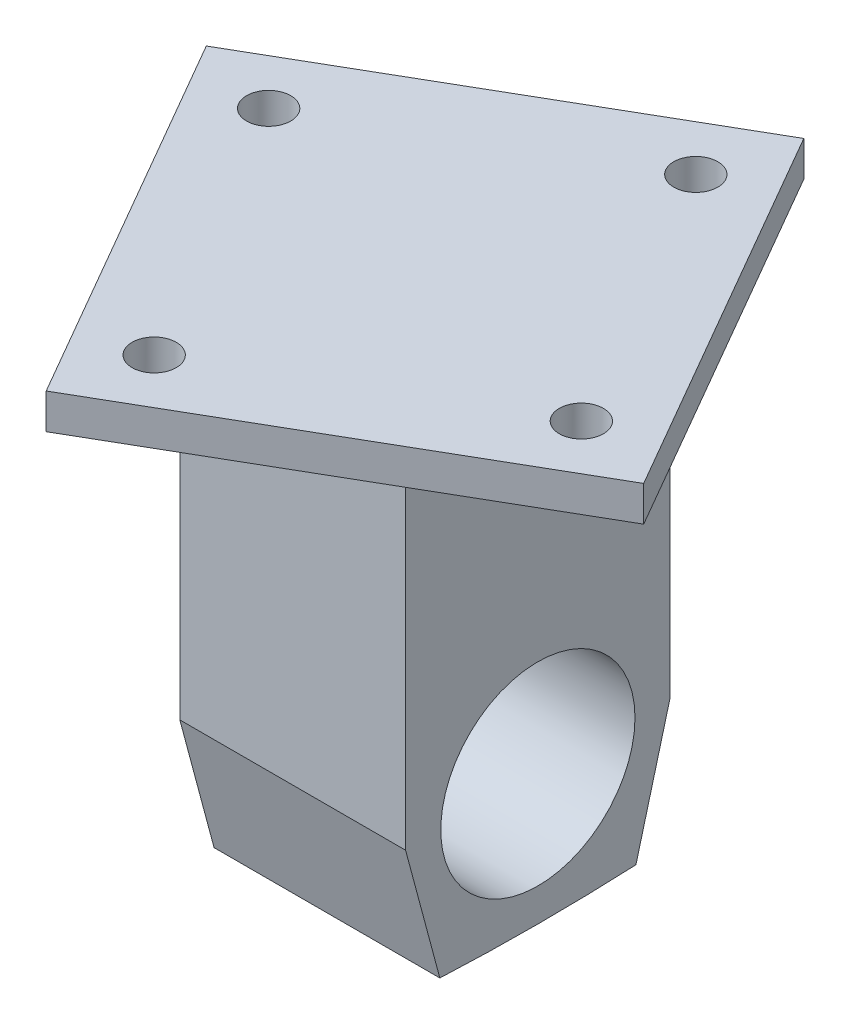
SolidWorks part; units mm, degrees
material "ABS"
ref_plane "Front Plane" through (0, 0, 0) normal (0, 0, 1) x (1, 0, 0)
ref_plane "Top Plane" through (0, 0, 0) normal (0, 1, 0) x (1, 0, 0)
ref_plane "Right Plane" through (0, 0, 0) normal (1, 0, 0) x (0, 0, -1)
sketch "Sketch1" plane through (0, 0, 0) normal (0, 1, 0) x (1, 0, 0)
  line L1 (-16.256, -19.05) -> (16.256, -19.05)
  line L2 (-16.256, -19.05) -> (-16.256, 19.05)
  line L3 (-16.256, 19.05) -> (16.256, 19.05)
  line L4 (16.256, -19.05) -> (16.256, 19.05)
  line L5 (-16.256, -19.05) -> (16.256, 19.05) construction
  line L6 (-16.256, 19.05) -> (16.256, -19.05) construction
  point P0 (0, 0)
extrude "Boss-Extrude1" add sketch "Sketch1" along normal blind 50.292
sketch "Sketch2" plane through (16.256, 0, 0) normal (1, 0, 0) x (0, 0, -1)
  line L0 (-19.05, 0) -> (-14.1195, -18.4009)
  line L1 (19.05, 0) -> (14.1195, -18.4009)
  line L2 (-19.05, 0) -> (19.05, 0)
  line L3 (-19.05, 0) -> (19.05, 0) construction
  arc A1 (14.1195, -18.4009) -> (-14.1195, -18.4009) centre (0, 281.2546) cw
  dimension "D1" = 19.05
  dimension "D2" = 19.05
  dimension "D3" = 75
  dimension "D4" = 75
extrude "Boss-Extrude2" add sketch "Sketch2" against normal up to vertex (32.512 mm away) contours L0 A1 L1 L2 up to point (-16.256, 0, -19.05)
sketch "Sketch3" plane through (16.256, 0, 0) normal (1, 0, 0) x (0, 0, -1)
  circle A0 centre (0, 0) radius 13.9872
extrude "Cut-Extrude1" cut sketch "Sketch3" against normal blind 127 contours A0
sketch "Sketch4" plane through (0, 50.292, 0) normal (0, 1, 0) x (1, 0, 0)
  line L0 (-46.8473, 12.5527) -> (46.8473, -12.5527) construction
  line L5 (-13.6389, -50.901) -> (13.6389, 50.901) construction
  line L6 (43.0243, -11.5283) -> (-11.5283, -43.0243)
  line L11 (-11.5283, -43.0243) -> (-43.0243, 11.5283)
  line L12 (-43.0243, 11.5283) -> (11.5283, 43.0243)
  line L13 (11.5283, 43.0243) -> (43.0243, -11.5283)
  line L14 (-11.5283, -43.0243) -> (11.5283, 43.0243) construction
  line L15 (-43.0243, 11.5283) -> (43.0243, -11.5283) construction
  point P1 (0, 0)
  point P4 (0, 0)
  point P11 (0, 0)
  dimension "D1" = 62.992
  dimension "D2" = 62.992
  dimension "D3" = 0
  dimension "D4" = 0
extrude "Boss-Extrude3" add sketch "Sketch4" along normal blind 5.08
sketch "Sketch5" plane through (0, 55.372, 0) normal (0, 1, 0) x (1, 0, 0)
  line L2 (30.7571, -8.2413) -> (43.0243, -11.5283) construction
  line L3 (-8.2413, -30.7571) -> (-11.5283, -43.0243) construction
  line L4 (-30.7571, 8.2413) -> (-43.0243, 11.5283) construction
  line L5 (8.2413, 30.7571) -> (11.5283, 43.0243) construction
  line L6 (11.5283, 43.0243) -> (-43.0243, 11.5283) construction
  line L7 (43.0243, -11.5283) -> (11.5283, 43.0243) construction
  line L8 (-43.0243, 11.5283) -> (-11.5283, -43.0243) construction
  circle A0 centre (30.7571, -8.2413) radius 3.175
  circle A1 centre (-8.2413, -30.7571) radius 3.175
  circle A2 centre (8.2413, 30.7571) radius 3.175
  circle A3 centre (-30.7571, 8.2413) radius 3.175
  dimension "D2" = 6.35
  dimension "D4" = 6.35
  dimension "D11" = 6.35
  dimension "D12" = 6.35
  dimension "D1" = 12.7
  dimension "D3" = 45
  dimension "D5" = 12.7
  dimension "D6" = 45
  dimension "D7" = 12.7
  dimension "D8" = 45
  dimension "D9" = 12.7
  dimension "D10" = 45
extrude "Cut-Extrude2" cut sketch "Sketch5" against normal through all
